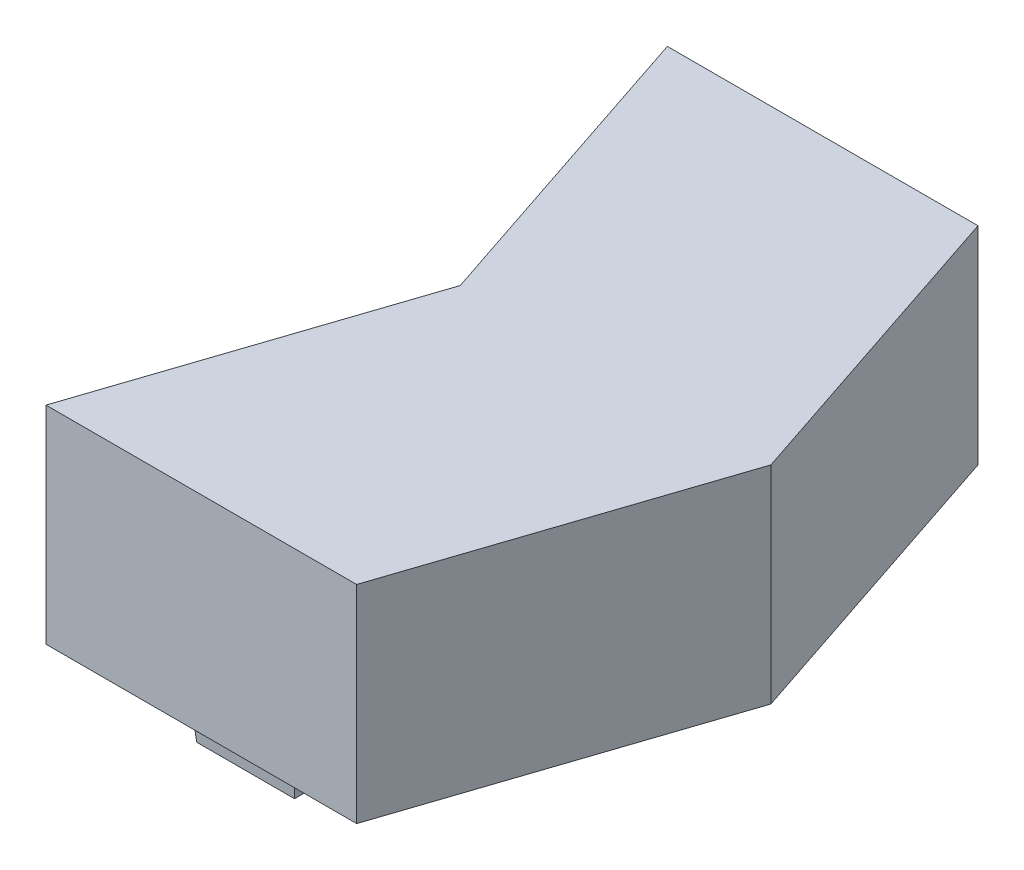
SolidWorks part; units mm, degrees
ref_plane "Front Plane" through (0, 0, 0) normal (0, 0, 1) x (1, 0, 0)
ref_plane "Top Plane" through (0, 0, 0) normal (0, 1, 0) x (1, 0, 0)
ref_plane "Right Plane" through (0, 0, 0) normal (1, 0, 0) x (0, 0, -1)
sketch "Sketch1" plane through (0, 0, 0) normal (0, 1, 0) x (1, 0, 0)
  line L0 (0, 0) -> (19.05, 0)
  line L1 (19.05, 0) -> (25.4, 19.05)
  line L2 (25.4, 19.05) -> (19.05, 38.1)
  line L3 (19.05, 38.1) -> (0, 38.1)
  line L4 (0, 38.1) -> (6.35, 19.05)
  line L5 (6.35, 19.05) -> (0, 0)
  dimension "D1" = 19.05
  dimension "D2" = 38.1
  dimension "D3" = 6.35
  dimension "D5" = 19.05
extrude "Boss-Extrude1" add sketch "Sketch1" along normal blind 12.7
sketch "Sketch2" plane through (0, 0, 0) normal (0, -1, 0) x (1, 0, 0)
  line L0 (25.4, -19.05) -> (6.35, -19.05) construction
  line L1 (6.35, -19.05) -> (0, 0) construction
  circle A0 centre (15.24, -19.05) radius 5.635
  dimension "D1" = 11.27
  dimension "D2" = 8.89
extrude "Haptic Motor Cutout" cut sketch "Sketch2" against normal blind 9.558 contours A0
sketch "Sketch3" plane through (0, 0, 0) normal (0, -1, 0) x (1, 0, 0)
  line L8 (16.51, -24.54) -> (13.97, -24.54)
  line L9 (16.51, -24.54) -> (16.51, -28.35)
  line L10 (13.97, -24.54) -> (13.97, -28.35)
  line L11 (16.51, -28.35) -> (13.97, -28.35)
  circle A3 centre (15.24, -19.05) radius 5.635 construction
  dimension "D1" = 2.54
  dimension "D2" = 3.81
extrude "Haptic Wire Cutout" cut sketch "Sketch3" against normal blind 9.558
ref_plane "MidPlane" through (0, 0, -19.05) normal (0, 0, -1) x (-1, 0, 0)
sketch "Sketch4" plane through (0, 0, 0) normal (0, -1, 0) x (1, 0, 0)
  line L0 (19.05, -38.1) -> (0, -38.1) construction
  line L1 (13.97, -36.83) -> (7.62, -36.83)
  line L2 (13.97, -36.83) -> (13.97, -34.29)
  line L3 (13.97, -34.29) -> (7.62, -34.29)
  line L4 (7.62, -36.83) -> (7.62, -34.29)
  line L5 (0, -6.985) -> (0, 6.985) construction
  dimension "D1" = 2.54
  dimension "D2" = 6.35
  dimension "D3" = 1.27
  dimension "D4" = 7.62
extrude "Pins" add sketch "Sketch4" along normal blind 2.032 draft 5
mirror "Mirror1" about plane through (0, 0, -19.05) normal (0, 0, -1) of "Pins"
ref_point "Point1"
ref_axis "Axis1" through (0, 12.7, -38.1) along (0, 0, 1)
sketch "Sketch5" plane through (0, 12.7, 0) normal (0, 1, 0) x (1, 0, 0)
  line L0 (0, 38.1) -> (0, 0) construction
  line L1 (0, 19.05) -> (25.4, 19.05) construction
equation "\"Arrow Height\"= 1.5in"
equation "\"Button Height\"= 2in"
equation "\"Button Width\"= 4in"
equation "\"Haptic Diameter\"= 10mm"
equation "\"Haptic Thickness\"= 2.7mm"
equation "\"D2@Sketch1\"=\"Arrow Height\""
equation "\"D5@Sketch1\"=\"Arrow Height\"/2"
equation "\"D1@Sketch2\"=\"Haptic Diameter\"+.05in"
equation "\"D1@Haptic Motor Cutout\"=\"Haptic Thickness\" + .02+.25"
equation "\"D1@Haptic Wire Cutout\"=\"Haptic Thickness\"+.02+.25"
equation "\"Arrow Spacing\"= 1in"
equation "\"Arrow Width\"= 01in"
equation "\"Haptic Wire Angle\"= 63.43"
equation "\"Haptic Wire Width\"= .1in"
equation "\"Haptic Wire Height\"= .15in"
